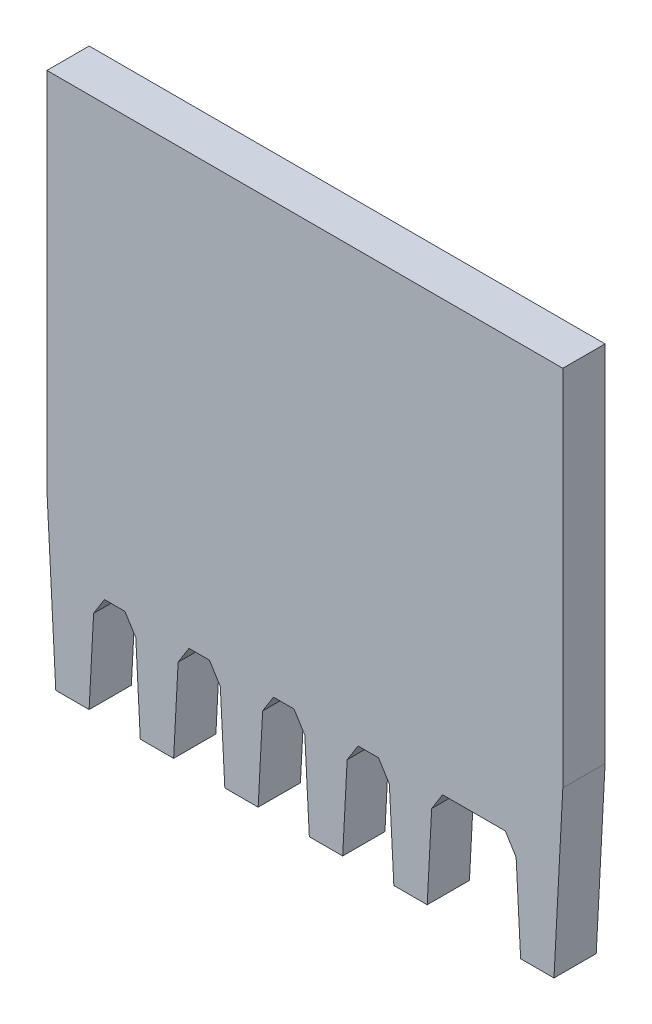
SolidWorks part; units mm, degrees
ref_plane "Front Plane" through (0, 0, 0) normal (0, 0, 1) x (1, 0, 0)
ref_plane "Top Plane" through (0, 0, 0) normal (0, 1, 0) x (1, 0, 0)
ref_plane "Right Plane" through (0, 0, 0) normal (1, 0, 0) x (0, 0, -1)
sketch "Sketch1" plane through (0, 0, 0) normal (0, 0, 1) x (1, 0, 0)
  line L0 (0, 0) -> (0, 18.9) construction
  line L1 (0, 18.9) -> (18.3124, 18.9) construction
  line L2 (18.3124, 18.9) -> (18.3124, 0) construction
  line L3 (18.3124, 0) -> (0, 0) construction
  line L4 (0, 3) -> (18.3124, 3) construction
  line L5 (0, 6) -> (18.3124, 6) construction
  line L6 (0.9062, 6) -> (0.9062, 0) construction
  line L7 (3.9062, 6) -> (3.9062, 0) construction
  line L8 (6.9062, 6) -> (6.9062, 0) construction
  line L9 (9.9062, 6) -> (9.9062, 0) construction
  line L10 (12.9062, 6) -> (12.9062, 0) construction
  line L11 (17.4062, 6) -> (17.4062, 0) construction
  line L12 (0.9062, 3) -> (3.9062, 3) construction
  line L13 (3.9062, 3) -> (6.9062, 3) construction
  line L14 (6.9062, 3) -> (9.9062, 3) construction
  line L15 (9.9062, 3) -> (12.9062, 3) construction
  line L16 (12.9062, 3) -> (17.4062, 3) construction
  line L17 (0.9062, 3) -> (0, 3) construction
  line L18 (17.4062, 3) -> (18.3124, 3) construction
  line L19 (2.4062, 3) -> (2.4062, 0) construction
  line L20 (5.4062, 3) -> (5.4062, 0) construction
  line L21 (8.4062, 3) -> (8.4062, 0) construction
  line L22 (11.4062, 3) -> (11.4062, 0) construction
  line L23 (15.1562, 3) -> (15.1562, 0) construction
  line L24 (14.4062, 3.75) -> (15.9062, 3.75) construction
  line L25 (0, 6) -> (0.3144, 0)
  line L26 (0.3144, 0) -> (1.4979, 0)
  line L27 (1.4979, 0) -> (1.6572, 3.0393)
  line L28 (3.1552, 3.0393) -> (3.3144, 0)
  line L29 (3.3144, 0) -> (4.4979, 0)
  line L30 (4.4979, 0) -> (4.6572, 3.0393)
  line L31 (6.1552, 3.0393) -> (6.3144, 0)
  line L32 (6.3144, 0) -> (7.4979, 0)
  line L33 (7.4979, 0) -> (7.6572, 3.0393)
  line L34 (9.1552, 3.0393) -> (9.3144, 0)
  line L35 (9.3144, 0) -> (10.4979, 0)
  line L36 (10.4979, 0) -> (10.6572, 3.0393)
  line L37 (12.1552, 3.0393) -> (12.3144, 0)
  line L38 (12.3144, 0) -> (13.4979, 0)
  line L39 (13.4979, 0) -> (13.6572, 3.0393)
  line L40 (16.6552, 3.0393) -> (16.8144, 0)
  line L41 (16.8144, 0) -> (17.9979, 0)
  line L42 (17.9979, 0) -> (18.3124, 6)
  line L44 (1.6572, 3.0393) -> (2.0426, 3.656)
  line L45 (0, 6) -> (0, 18.9)
  line L46 (0, 18.9) -> (18.3124, 18.9)
  line L47 (18.3124, 18.9) -> (18.3124, 6)
  line L48 (9.1562, 18.9) -> (9.1562, 6) construction
  line L49 (2.0426, 3.656) -> (2.7698, 3.656)
  line L50 (2.7698, 3.656) -> (3.1552, 3.0393)
  line L51 (4.6572, 3.0393) -> (5.0426, 3.656)
  line L52 (5.0426, 3.656) -> (5.7698, 3.656)
  line L53 (5.7698, 3.656) -> (6.1552, 3.0393)
  line L54 (7.6572, 3.0393) -> (8.0426, 3.656)
  line L55 (8.0426, 3.656) -> (8.7698, 3.656)
  line L56 (8.7698, 3.656) -> (9.1552, 3.0393)
  line L57 (10.6572, 3.0393) -> (11.0426, 3.656)
  line L58 (11.0426, 3.656) -> (11.7698, 3.656)
  line L59 (11.7698, 3.656) -> (12.1552, 3.0393)
  line L60 (13.6572, 3.0393) -> (14.0426, 3.656)
  line L61 (14.0426, 3.656) -> (16.2698, 3.656)
  line L62 (16.2698, 3.656) -> (16.6552, 3.0393)
  arc A0 (3.1552, 3.0393) -> (1.6572, 3.0393) centre (2.4062, 3) ccw construction
  arc A1 (6.1552, 3.0393) -> (4.6572, 3.0393) centre (5.4062, 3) ccw construction
  arc A2 (9.1552, 3.0393) -> (7.6572, 3.0393) centre (8.4062, 3) ccw construction
  arc A3 (12.1552, 3.0393) -> (10.6572, 3.0393) centre (11.4062, 3) ccw construction
  arc A4 (13.6572, 3.0393) -> (14.4062, 3.75) centre (14.4062, 3) cw construction
  arc A5 (16.6552, 3.0393) -> (15.9062, 3.75) centre (15.9062, 3) ccw construction
  dimension "D7" = 0.75
  dimension "D1" = 3
  dimension "D2" = 6
  dimension "D3" = 12.9
  dimension "D4" = 3
  dimension "D6" = 4.5
  dimension "D8" = 3
  dimension "D9" = 18.3124
  dimension "D10" = 18.9
extrude "Boss-Extrude1" add sketch "Sketch1" along normal blind 1.5
sketch "Sketch3" plane through (0, 0, 0) normal (0, 0, 1) x (1, 0, 0)
  line L0 (-0.4005, 6) -> (18.7129, 6)
  line L1 (18.7129, 3) -> (-0.4005, 3) construction
  line L2 (-0.4005, 0) -> (18.7129, 0) construction
  line L3 (-0.4005, -0.5) -> (18.7129, -0.5) construction
  line L4 (18.7129, -0.5) -> (18.7129, 6) construction
  line L5 (-0.4005, 6) -> (-0.4005, -0.5) construction
  line L6 (18.3124, 0) -> (0, 0) construction
  line L7 (0, 3) -> (18.3124, 3) construction
  line L8 (0, 6) -> (18.3124, 6) construction
  line L9 (0.3407, -0.5) -> (0, 6) construction
  line L10 (18.3124, 6) -> (17.9717, -0.5) construction
  line L11 (17.9979, 0) -> (18.3124, 6) construction
  line L12 (0, 6) -> (0.3144, 0) construction
  line L13 (5.4062, 6) -> (5.4062, -0.5) construction
  line L14 (3.9062, 6) -> (3.9062, -0.5) construction
  line L15 (5.4062, 3) -> (5.4062, 0) construction
  line L16 (3.1572, 3) -> (3.3407, -0.5) construction
  line L17 (2.7567, 3) -> (2.9401, -0.5)
  line L18 (3.1552, 3.0393) -> (3.3144, 0) construction
  line L19 (2.9401, -0.5) -> (4.8723, -0.5)
  line L20 (4.8723, -0.5) -> (5.0557, 3)
  line L21 (2.8484, 1.25) -> (3.2478, 1.2709) construction
  line L22 (5.9401, -0.5) -> (5.7567, 3)
  line L26 (7.8723, -0.5) -> (5.9401, -0.5)
  line L27 (8.0557, 3) -> (7.8723, -0.5)
  line L30 (2.4062, -0.5) -> (2.4062, 6) construction
  line L31 (2.4062, 3) -> (2.4062, 0) construction
  line L32 (8.4062, 6) -> (8.4062, -0.5) construction
  line L34 (11.4062, -0.5) -> (11.4062, 6) construction
  line L35 (15.1562, -0.5) -> (15.1562, 6) construction
  line L36 (8.4062, 3) -> (8.4062, 0) construction
  line L37 (11.4062, 3) -> (11.4062, 0) construction
  line L38 (15.1562, 3) -> (15.1562, 0) construction
  line L39 (10.8723, -0.5) -> (11.0557, 3)
  line L40 (8.9401, -0.5) -> (10.8723, -0.5)
  line L41 (8.7567, 3) -> (8.9401, -0.5)
  line L42 (11.9401, -0.5) -> (11.7567, 3)
  line L43 (13.8723, -0.5) -> (11.9401, -0.5)
  line L44 (14.0557, 3) -> (13.8723, -0.5)
  line L45 (16.4401, -0.5) -> (18.3723, -0.5)
  line L46 (16.2567, 3) -> (16.4401, -0.5)
  line L47 (18.3723, -0.5) -> (18.7129, 6)
  line L48 (1.8723, -0.5) -> (-0.0599, -0.5)
  line L49 (2.0557, 3) -> (1.8723, -0.5)
  line L50 (-0.0599, -0.5) -> (-0.4005, 6)
  line L51 (16.2567, 3) -> (14.0557, 3)
  line L52 (11.7567, 3) -> (11.0557, 3)
  line L53 (8.7567, 3) -> (8.0557, 3)
  line L54 (5.7567, 3) -> (5.0557, 3)
  line L55 (2.7567, 3) -> (2.0557, 3)
  dimension "D1" = 0.5
  dimension "D2" = 0.4
ref_plane "Plane1" through (3.9062, 0, 0) normal (1, 0, 0) x (0, 0, -1)
sketch "Sketch4" plane through (3.9062, 0, 0) normal (1, 0, 0) x (0, 0, -1)
  line L0 (0, 6) -> (0, -0.5) construction
  line L1 (0.6, 6) -> (-2.1, 6) construction
  line L2 (0.6, 6) -> (0.6, -0.5) construction
  line L3 (0.6, -0.5) -> (-2.1, -0.5) construction
  line L4 (-2.1, 6) -> (-2.1, -0.5) construction
  line L5 (-0.75, -0.5) -> (-0.75, 6) construction
  line L6 (-1.5, 6) -> (-1.5, -0.5) construction
  line L7 (0.6, 2.4005) -> (-2.1, 2.4005) construction
  line L8 (0.3, 6) -> (0.3, -0.5) construction
  line L9 (0.6, 2.4005) -> (3.846, 6) construction
  line L10 (2.2302, 6) -> (0.6, 4.1923) construction
  line L11 (0.6, 4.1923) -> (1.7139, 3.1878) construction
  line L12 (1.7139, 3.1878) -> (4.25, 6)
  line L13 (4.25, 6) -> (0.6, 6) construction
  line L14 (0.3, 1) -> (-1.8, 1) construction
  line L15 (-2.1, 0) -> (0.6, 0) construction
  line L16 (1.7139, 3.1878) -> (1.4912, 3.3887)
  line L17 (1.4912, 3.3887) -> (0.6, 2.4005)
  line L18 (-3.2139, 3.1878) -> (-5.75, 6)
  line L19 (-3.2139, 3.1878) -> (-2.9912, 3.3887)
  line L20 (-2.9912, 3.3887) -> (-2.1, 2.4005)
  line L21 (-2.1, 6) -> (-5.75, 6) construction
  line L22 (0.6, 3.0724) -> (3.2401, 6) construction
  arc A0 (0.4965, 2.2224) -> (0.6, -0.5) centre (4.2, 1) ccw
  arc A1 (0.6, 2.4005) -> (0.4965, 2.2224) centre (0.9713, 2.0656) ccw
  arc A2 (-2.1, 2.4005) -> (-1.9965, 2.2224) centre (-2.4713, 2.0656) cw
  arc A3 (-1.9965, 2.2224) -> (-2.1, -0.5) centre (-5.7, 1) cw
  dimension "D6" = 0.5
  dimension "D1" = 0.6
  dimension "D2" = 0.3
  dimension "D3" = 1.5
  dimension "D4" = 1
  dimension "D5" = 0.3
  dimension "D7" = 10
sketch "Sketch5" plane through (0, 0, 0) normal (1, 0, 0) x (0, 0, -1)
  line L0 (2.2302, 6) -> (0.6, 4.1923) construction
  line L1 (0.6, 4.1923) -> (1.7139, 3.1878) construction
  line L2 (1.7139, 3.1878) -> (4.25, 6) construction
  line L3 (2.2302, 6) -> (0.6, 4.1923) construction
  line L4 (0.6, 4.1923) -> (1.7139, 3.1878) construction
  line L5 (1.7139, 3.1878) -> (4.25, 6) construction
ref_plane "Plane2" through (0, 2.6105, -2.3541) normal (0, 0.7426, -0.6697) x (1, 0, 0)
sketch "Sketch6" plane through (0, 2.6105, -2.3541) normal (0, 0.7426, -0.6697) x (1, 0, 0)
  line L1 (3.9062, -2.362) -> (3.9062, -0.862) construction
  line L2 (3.9062, -2.362) -> (3.9062, -5.0612) construction
  line L3 (4.6562, -5.0612) -> (3.1562, -5.0612)
  line L4 (4.6562, -1.612) -> (3.1562, -1.612) construction
  line L5 (3.1562, -1.612) -> (3.1562, -5.0612)
  line L6 (4.6562, -1.612) -> (4.6562, -5.0612)
  line L10 (2.4062, -5.0612) -> (15.1562, -5.0612) construction
  line L11 (15.1562, -5.0612) -> (15.1562, -0.862) construction
  line L12 (15.1562, -0.862) -> (2.4062, -0.862) construction
  line L13 (2.4062, -0.862) -> (2.4062, -5.0612) construction
  line L14 (15.1562, 0.3349) -> (15.1562, -4.0182) construction
  line L15 (2.4062, 0.3349) -> (2.4062, -4.0182) construction
  line L16 (11.4062, -5.0612) -> (11.4062, -0.862) construction
  line L17 (8.4062, -5.0612) -> (8.4062, -0.862) construction
  line L18 (5.4062, -5.0612) -> (5.4062, -0.862) construction
  line L19 (5.4062, -4.0182) -> (5.4062, 0.3349) construction
  line L20 (8.4062, -4.0182) -> (8.4062, 0.3349) construction
  line L21 (11.4062, 0.3349) -> (11.4062, -4.0182) construction
  line L22 (0.1562, -1.612) -> (0.1562, -5.0612)
  line L23 (0.1562, -5.0612) -> (1.6562, -5.0612)
  line L24 (1.6562, -1.612) -> (1.6562, -5.0612)
  line L25 (7.6562, -1.612) -> (7.6562, -5.0612)
  line L26 (6.1562, -5.0612) -> (7.6562, -5.0612)
  line L27 (6.1562, -1.612) -> (6.1562, -5.0612)
  line L28 (10.6562, -1.612) -> (10.6562, -5.0612)
  line L29 (10.6562, -5.0612) -> (9.1562, -5.0612)
  line L30 (9.1562, -1.612) -> (9.1562, -5.0612)
  line L31 (13.6562, -1.612) -> (13.6562, -5.0612)
  line L32 (12.1562, -5.0612) -> (13.6562, -5.0612)
  line L33 (12.1562, -1.612) -> (12.1562, -5.0612)
  line L34 (18.1562, -1.612) -> (18.1562, -5.0612)
  line L35 (18.1562, -5.0612) -> (16.6562, -5.0612)
  line L36 (16.6562, -1.612) -> (16.6562, -5.0612)
  circle A0 centre (3.9062, -1.612) radius 0.75 construction
  arc A1 (4.6562, -1.612) -> (3.1562, -1.612) centre (3.9062, -1.612) ccw
  arc A2 (0.1562, -1.612) -> (1.6562, -1.612) centre (0.9062, -1.612) cw
  arc A3 (6.1562, -1.612) -> (7.6562, -1.612) centre (6.9062, -1.612) cw
  arc A4 (10.6562, -1.612) -> (9.1562, -1.612) centre (9.9062, -1.612) ccw
  arc A5 (12.1562, -1.612) -> (13.6562, -1.612) centre (12.9062, -1.612) cw
  arc A6 (18.1562, -1.612) -> (16.6562, -1.612) centre (17.4062, -1.612) ccw
ref_plane "Plane3" through (0, 1.6223, -1.463) normal (0, 0.7426, -0.6697) x (1, 0, 0)
sketch "Sketch7" plane through (0, 1.6223, -1.463) normal (0, 0.7426, -0.6697) x (1, 0, 0)
  line L0 (3.1562, -1.612) -> (3.1562, -5.0612) construction
  line L1 (4.6562, -5.0612) -> (3.1562, -5.0612) construction
  line L2 (4.6562, -1.612) -> (4.6562, -5.0612) construction
  line L3 (3.1562, -1.612) -> (3.1562, -5.0612) construction
  line L4 (4.6562, -5.0612) -> (3.1562, -5.0612) construction
  line L5 (4.6562, -1.612) -> (4.6562, -5.0612) construction
  line L6 (3.9062, -0.862) -> (3.9062, -5.0612) construction
  line L7 (4.6562, -1.612) -> (3.1562, -1.612) construction
  line L8 (4.6562, -2.362) -> (3.1562, -2.362) construction
  line L9 (3.4562, -1.612) -> (3.4562, -2.362)
  line L10 (3.4562, -2.362) -> (4.3562, -2.362)
  line L11 (4.3562, -2.362) -> (4.3562, -1.612)
  line L12 (2.4062, -0.862) -> (2.4062, -5.0612) construction
  line L13 (2.4062, -5.0612) -> (15.1562, -5.0612) construction
  line L14 (15.1562, -0.862) -> (2.4062, -0.862) construction
  line L15 (5.4062, -5.0612) -> (5.4062, -0.862) construction
  line L16 (8.4062, -5.0612) -> (8.4062, -0.862) construction
  line L17 (11.4062, -5.0612) -> (11.4062, -0.862) construction
  line L18 (15.1562, -5.0612) -> (15.1562, -0.862) construction
  line L19 (2.4062, -0.862) -> (2.4062, -5.0612) construction
  line L20 (2.4062, -5.0612) -> (15.1562, -5.0612) construction
  line L21 (15.1562, -0.862) -> (2.4062, -0.862) construction
  line L22 (5.4062, -5.0612) -> (5.4062, -0.862) construction
  line L23 (8.4062, -5.0612) -> (8.4062, -0.862) construction
  line L24 (11.4062, -5.0612) -> (11.4062, -0.862) construction
  line L25 (15.1562, -5.0612) -> (15.1562, -0.862) construction
  line L26 (0.4562, -2.362) -> (0.4562, -1.612)
  line L27 (1.3562, -2.362) -> (0.4562, -2.362)
  line L28 (1.3562, -1.612) -> (1.3562, -2.362)
  line L29 (7.3562, -2.362) -> (6.4562, -2.362)
  line L30 (7.3562, -1.612) -> (7.3562, -2.362)
  line L31 (6.4562, -2.362) -> (6.4562, -1.612)
  line L32 (9.4562, -1.612) -> (9.4562, -2.362)
  line L33 (10.3562, -2.362) -> (10.3562, -1.612)
  line L34 (9.4562, -2.362) -> (10.3562, -2.362)
  line L35 (13.3562, -1.612) -> (13.3562, -2.362)
  line L36 (12.4562, -2.362) -> (12.4562, -1.612)
  line L37 (13.3562, -2.362) -> (12.4562, -2.362)
  line L38 (16.9562, -1.612) -> (16.9562, -2.362)
  line L39 (17.8562, -2.362) -> (17.8562, -1.612)
  line L40 (16.9562, -2.362) -> (17.8562, -2.362)
  arc A0 (4.6562, -1.612) -> (3.1562, -1.612) centre (3.9062, -1.612) ccw construction
  arc A1 (4.6562, -1.612) -> (3.1562, -1.612) centre (3.9062, -1.612) ccw construction
  circle A2 centre (3.9062, -1.612) radius 0.45 construction
  arc A3 (4.3562, -1.612) -> (3.4562, -1.612) centre (3.9062, -1.612) ccw
  arc A4 (0.4562, -1.612) -> (1.3562, -1.612) centre (0.9062, -1.612) cw
  arc A5 (6.4562, -1.612) -> (7.3562, -1.612) centre (6.9062, -1.612) cw
  arc A6 (10.3562, -1.612) -> (9.4562, -1.612) centre (9.9062, -1.612) ccw
  arc A7 (12.4562, -1.612) -> (13.3562, -1.612) centre (12.9062, -1.612) cw
  arc A8 (17.8562, -1.612) -> (16.9562, -1.612) centre (17.4062, -1.612) ccw
ref_plane "bisect" through (0, 0, 0.75) normal (0, 0, 1) x (1, 0, 0)
ref_plane "insert_surface" through (0, 6, 0) normal (0, 1, 0) x (1, 0, 0)
sketch "Sketch8" plane through (0, 6, 0) normal (0, 1, 0) x (1, 0, 0)
  line L0 (18.7129, -0.75) -> (-0.4005, -0.75) construction
  line L1 (-0.4005, 0.6) -> (18.7129, 0.6)
  line L2 (-0.4005, 0.6) -> (-0.4005, -2.1)
  line L3 (-0.4005, -2.1) -> (18.7129, -2.1)
  line L4 (18.7129, 0.6) -> (18.7129, -2.1)
  line L5 (9.1562, 0.6) -> (9.1562, -2.1) construction
  line L6 (0, 0) -> (18.3124, 0) construction
  line L7 (0, 0) -> (0, -1.5) construction
  line L8 (0, -1.5) -> (18.3124, -1.5) construction
  line L9 (18.3124, 0) -> (18.3124, -1.5) construction
  line L10 (18.7129, 0.3) -> (-0.4005, 0.3) construction
  line L11 (18.7129, -1.8) -> (-0.4005, -1.8) construction
sketch "Sketch9" plane through (0, 0, 0) normal (0, 0, 1) x (1, 0, 0)
  line L0 (18.3723, -0.5) -> (18.7129, 6) construction
  line L1 (-0.4005, 6) -> (18.7129, 6) construction
  line L2 (-0.0599, -0.5) -> (-0.4005, 6) construction
  line L3 (1.8723, -0.5) -> (-0.0599, -0.5) construction
  line L4 (2.0557, 3) -> (1.8723, -0.5) construction
  line L5 (2.7567, 3) -> (2.0557, 3) construction
  line L6 (2.7567, 3) -> (2.9401, -0.5) construction
  line L7 (2.9401, -0.5) -> (4.8723, -0.5) construction
  line L8 (4.8723, -0.5) -> (5.0557, 3) construction
  line L9 (5.7567, 3) -> (5.0557, 3) construction
  line L10 (5.9401, -0.5) -> (5.7567, 3) construction
  line L11 (7.8723, -0.5) -> (5.9401, -0.5) construction
  line L12 (8.0557, 3) -> (7.8723, -0.5) construction
  line L13 (8.7567, 3) -> (8.0557, 3) construction
  line L14 (8.7567, 3) -> (8.9401, -0.5) construction
  line L15 (8.9401, -0.5) -> (10.8723, -0.5) construction
  line L16 (10.8723, -0.5) -> (11.0557, 3) construction
  line L17 (11.7567, 3) -> (11.0557, 3) construction
  line L18 (11.9401, -0.5) -> (11.7567, 3) construction
  line L19 (13.8723, -0.5) -> (11.9401, -0.5) construction
  line L20 (14.0557, 3) -> (13.8723, -0.5) construction
  line L21 (16.2567, 3) -> (14.0557, 3) construction
  line L22 (16.2567, 3) -> (16.4401, -0.5) construction
  line L23 (16.4401, -0.5) -> (18.3723, -0.5) construction
  line L24 (18.3723, -0.5) -> (18.7129, 6)
  line L25 (-0.4005, 6) -> (18.7129, 6) construction
  line L26 (-0.0599, -0.5) -> (-0.4005, 6)
  line L27 (1.8723, -0.5) -> (-0.0599, -0.5)
  line L28 (2.0557, 3) -> (1.8723, -0.5)
  line L29 (2.7567, 3) -> (2.0557, 3) construction
  line L30 (2.7567, 3) -> (2.9401, -0.5)
  line L31 (2.9401, -0.5) -> (4.8723, -0.5)
  line L32 (4.8723, -0.5) -> (5.0557, 3)
  line L33 (5.7567, 3) -> (5.0557, 3) construction
  line L34 (5.9401, -0.5) -> (5.7567, 3)
  line L35 (7.8723, -0.5) -> (5.9401, -0.5)
  line L36 (8.0557, 3) -> (7.8723, -0.5)
  line L37 (8.7567, 3) -> (8.0557, 3) construction
  line L38 (8.7567, 3) -> (8.9401, -0.5)
  line L39 (8.9401, -0.5) -> (10.8723, -0.5)
  line L40 (10.8723, -0.5) -> (11.0557, 3)
  line L41 (11.7567, 3) -> (11.0557, 3) construction
  line L42 (11.9401, -0.5) -> (11.7567, 3)
  line L43 (13.8723, -0.5) -> (11.9401, -0.5)
  line L44 (14.0557, 3) -> (13.8723, -0.5)
  line L45 (16.2567, 3) -> (14.0557, 3) construction
  line L46 (16.2567, 3) -> (16.4401, -0.5)
  line L47 (16.4401, -0.5) -> (18.3723, -0.5)
  line L48 (16.2567, 3) -> (16.2567, 6)
  line L49 (14.0557, 3) -> (14.0557, 6)
  line L50 (11.7567, 3) -> (11.7567, 6)
  line L51 (18.7129, 6) -> (-0.4005, 6) construction
  line L52 (11.0557, 3) -> (11.0557, 6)
  line L53 (-0.4005, 6) -> (18.7129, 6) construction
  line L54 (8.7567, 3) -> (8.7567, 6)
  line L55 (8.0557, 3) -> (8.0557, 6)
  line L58 (5.7567, 3) -> (5.7567, 6)
  line L60 (5.0557, 3) -> (5.0557, 6)
  line L62 (15.1562, -0.5) -> (15.1562, 6) construction
  line L63 (15.1562, -0.5) -> (15.1562, 6) construction
  line L64 (2.7567, 3) -> (2.7567, 6)
  line L65 (2.0557, 3) -> (2.0557, 6)
  line L67 (18.7129, 6) -> (16.2567, 6)
  line L68 (14.0557, 6) -> (11.7567, 6)
  line L69 (11.0557, 6) -> (8.7567, 6)
  line L70 (8.0557, 6) -> (5.7567, 6)
  line L71 (5.0557, 6) -> (2.7567, 6)
  line L72 (2.0557, 6) -> (-0.4005, 6)
sketch "Sketch10" plane through (0, 6, 0) normal (0, 1, 0) x (1, 0, 0)
  line L0 (9.1562, 0) -> (9.1562, -5) construction
  line L1 (-0.8438, 5) -> (19.1562, 5)
  line L2 (-0.8438, 5) -> (-0.8438, -5)
  line L3 (-0.8438, -5) -> (19.1562, -5)
  line L4 (19.1562, 5) -> (19.1562, -5)
  line L5 (0, 0) -> (18.3124, 0) construction
  line L6 (9.1562, 0) -> (9.1562, 5) construction
  line L7 (9.1562, 0) -> (19.1562, 0) construction
  line L8 (9.1562, 0) -> (-0.8438, 0) construction
  dimension "D1" = 20
  dimension "D2" = 10
